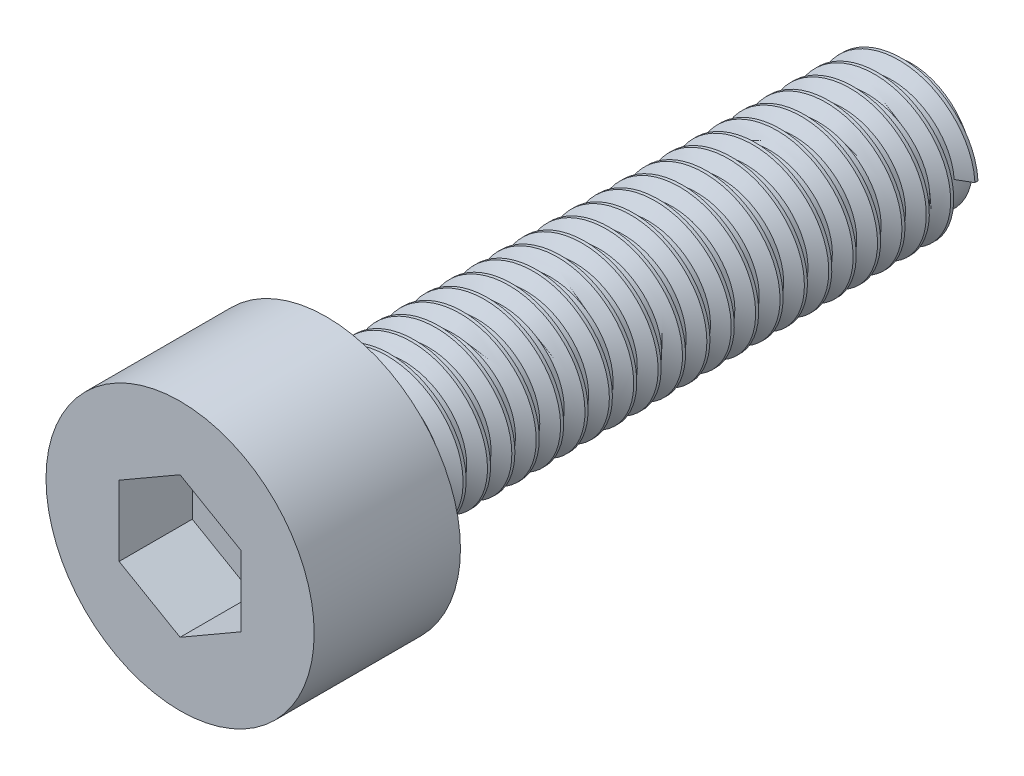
SolidWorks part; units mm, degrees
material "Cast Carbon Steel"
ref_plane "Front Plane" through (0, 0, 0) normal (0, 0, 1) x (1, 0, 0)
ref_plane "Top Plane" through (0, 0, 0) normal (0, 1, 0) x (1, 0, 0)
ref_plane "Right Plane" through (0, 0, 0) normal (1, 0, 0) x (0, 0, -1)
sketch "Sketch1" plane through (0, 0, 0) normal (0, 0, 1) x (1, 0, 0)
  circle A0 centre (0, 0) radius 2.75
  dimension "D1" = 5.5
extrude "Boss-Extrude1" add sketch "Sketch1" along normal blind 3
sketch "Sketch2" plane through (0, 0, 0) normal (0, 0, -1) x (-1, 0, 0)
  circle A0 centre (0, 0) radius 1.25
  dimension "D1" = 2.5
extrude "Boss-Extrude2" add sketch "Sketch2" along normal blind 12
sketch "Sketch3" plane through (0, 0, 3) normal (0, 0, 1) x (1, 0, 0)
  line L1 (0, 1.4434) -> (-1.25, 0.7217)
  line L2 (-1.25, 0.7217) -> (-1.25, -0.7217)
  line L3 (-1.25, -0.7217) -> (0, -1.4434)
  line L4 (0, -1.4434) -> (1.25, -0.7217)
  line L5 (1.25, -0.7217) -> (1.25, 0.7217)
  line L6 (1.25, 0.7217) -> (0, 1.4434)
  circle A0 centre (0, 0) radius 1.25 construction
  dimension "D1" = 2.5
extrude "Cut-Extrude1" cut sketch "Sketch3" against normal blind 1.5
thread "Thread1" pitch 0.5 method extrude profile "Thread Profile1" start angle 0, offset 0, length 12, pitch 0.5, diameter 2.5
ref_plane "Plane1" through (1.25, 0, -12) normal (0, -1, 0) x (1, 0, 0)
sketch "Thread Profile1" plane through (1.25, 0, -12) normal (0, -1, 0) x (1, 0, 0)
  line L0 (0, 0) -> (0, 0.5) construction
  line L1 (0, 0) -> (0.2706, 0.1562)
  line L2 (0.2706, 0.1562) -> (0.2706, 0.2187)
  line L3 (0.2706, 0.2187) -> (0, 0.375)
  line L4 (0.2706, 0.1875) -> (0, 0.1875) construction
  line L11 (0, 0) -> (0, 0.375)
  point P2 (0, 0)
  dimension "Pitch" = 0.5
  dimension "Profile_Angle" = 60
  dimension "Profile_Land" = 0.0625
  dimension "Profile_Height" = 0.2706
